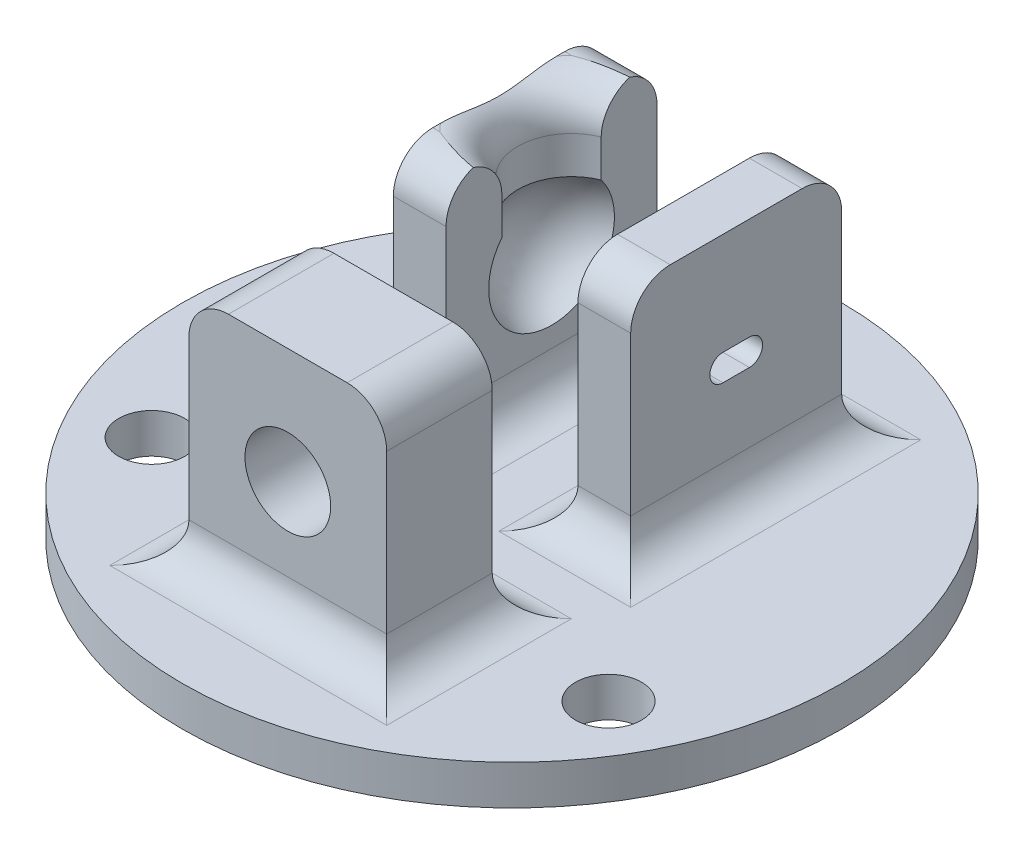
SolidWorks part; units mm, degrees
ref_plane "Front Plane" through (0, 0, 0) normal (0, 0, 1) x (1, 0, 0)
ref_plane "Top Plane" through (0, 0, 0) normal (0, 1, 0) x (1, 0, 0)
ref_plane "Right Plane" through (0, 0, 0) normal (1, 0, 0) x (0, 0, -1)
sketch "Sketch1" plane through (0, 0, 0) normal (0, 1, 0) x (1, 0, 0)
  circle A0 centre (0, 0) radius 25
  circle A1 centre (0, 20) radius 2.5
  circle A2 centre (17.3205, -10) radius 2.5
  circle A3 centre (-17.3205, -10) radius 2.5
  point P12 (0, 0)
  dimension "D1" = 50
  dimension "D2" = 5
  dimension "D3" = 20
  dimension "D4" = 3
extrude "Boss-Extrude1" add sketch "Sketch1" along normal blind 2 and the other way blind 1
sketch "Sketch2" plane through (0, 2, 0) normal (0, 1, 0) x (1, 0, 0)
  line L0 (0, 0) -> (0, 8) construction
  line L1 (0, 8) -> (-7, 8) construction
  line L2 (9, 0) -> (5, 0)
  line L3 (-9, 16) -> (-5, 16)
  line L4 (-9, 16) -> (-9, 0)
  line L5 (-9, 0) -> (-5, 0)
  line L6 (-5, 16) -> (-5, 0)
  line L7 (-9, 16) -> (-5, 0) construction
  line L8 (-9, 0) -> (-5, 16) construction
  line L9 (5, 16) -> (5, 0)
  line L10 (9, 16) -> (5, 16)
  line L11 (9, 16) -> (9, 0)
  dimension "D1" = 16
  dimension "D2" = 8
  dimension "D3" = 4
  dimension "D4" = 7
extrude "Boss-Extrude2" add sketch "Sketch2" along normal blind 18
sketch "Sketch3" plane through (5, 0, 0) normal (-1, 0, 0) x (0, 0, 1)
  line L0 (-8, 20) -> (-8, 2) construction
  line L1 (-16, 20) -> (0, 20) construction
  line L2 (-16, 2) -> (0, 2) construction
  circle A0 centre (-8, 11.25) radius 5.75
  dimension "D1" = 11.5
  dimension "D2" = 8.75
extrude "Cut-Extrude1" cut sketch "Sketch3" against normal blind 1.5
ref_plane "Plane1" through (-3.5, 0, 0) normal (-1, 0, 0) x (0, 0, 1)
sketch "Sketch4" plane through (-3.5, 0, 0) normal (-1, 0, 0) x (0, 0, 1)
  line L0 (-3, 11.2698) -> (-13, 11.2698) construction
  line L1 (-3, 11.2698) -> (-13, 11.2698)
  arc A0 (-3, 11.2698) -> (-13, 11.2698) centre (-8, 11.25) ccw
  dimension "D1" = 5
revolve "Cut-Revolve1" cut sketch "Sketch4" angle 180 about L0 reverse direction yes
sketch "Sketch5" plane through (0, 20, 0) normal (0, 1, 0) x (1, 0, 0)
  line L0 (-3.5, 6.325) -> (-3.5, -6.325) construction
  line L1 (-5, 0) -> (-5, 16) construction
  line L2 (-5, 11.7634) -> (-5, 4.2303)
  arc A0 (-5, 11.7634) -> (-5, 4.2303) centre (-3.5, 7.9969) ccw
  dimension "D1" = 1
extrude "Cut-Extrude2" cut sketch "Sketch5" against normal up to next
sketch "Sketch6" plane through (6.5, 0, 0) normal (-1, 0, 0) x (0, 0, 1)
  line L0 (-8, 11.25) -> (-9, 11.25) construction
  line L1 (-8, 11.25) -> (-7, 11.25) construction
  line L2 (-9, 11.25) -> (-7, 11.25) construction
  line L3 (-9, 12.25) -> (-7, 12.25)
  line L4 (-9, 10.25) -> (-7, 10.25)
  arc A0 (-9, 12.25) -> (-9, 10.25) centre (-9, 11.25) ccw
  arc A1 (-7, 10.25) -> (-7, 12.25) centre (-7, 11.25) ccw
  point P3 (-8, 11.25)
  dimension "D1" = 1
  dimension "D2" = 1
  dimension "D3" = 1
extrude "Cut-Extrude3" cut sketch "Sketch6" against normal up to next
fillet "Fillet1" radius 3 13 edges at (-7.5543, 20, -7.9969) (7, 2, -16) (9, 2, -8) (5, 2, -8) (-7, 2, -16) (-5, 2, -8) (-9, 2, -8) (7, 2, 0) (-7, 2, 0) (-7, 20, -16) (-7, 20, 0) (7, 20, -16) (7, 20, 0)
sketch "Sketch7" plane through (0, 2, 0) normal (0, 1, 0) x (1, 0, 0)
  line L0 (0, -25) -> (0, -13) construction
  line L2 (7.5, -9) -> (-7.5, -9)
  line L3 (7.5, -9) -> (7.5, -17)
  line L4 (7.5, -17) -> (-7.5, -17)
  line L5 (-7.5, -9) -> (-7.5, -17)
  line L6 (7.5, -9) -> (-7.5, -17) construction
  line L7 (7.5, -17) -> (-7.5, -9) construction
  circle A0 centre (0, 0) radius 25 construction
  dimension "D1" = 12
  dimension "D2" = 15
  dimension "D3" = 8
extrude "Boss-Extrude3" add sketch "Sketch7" along normal blind 18
sketch "Sketch8" plane through (0, 0, 17) normal (0, 0, 1) x (1, 0, 0)
  line L0 (0, 20) -> (0, 11.25) construction
  line L1 (-7.5, 20) -> (7.5, 20) construction
  circle A0 centre (0, 11.25) radius 3.25
  dimension "D2" = 6.5
  dimension "D1" = 8.75
extrude "Cut-Extrude4" cut sketch "Sketch8" against normal up to next
sketch "Sketch9" plane through (0, 0, 9) normal (0, 0, -1) x (-1, 0, 0)
  circle A0 centre (0, 11.25) radius 3.25
  circle A1 centre (0, 11.25) radius 2.25
  dimension "D1" = 4.5
extrude "Boss-Extrude4" add sketch "Sketch9" against normal blind 1
fillet "Fillet2" radius 3 6 edges at (7.5, 20, 13) (-7.5, 20, 13) (7.5, 2, 13) (0, 2, 9) (0, 2, 17) (-7.5, 2, 13)
